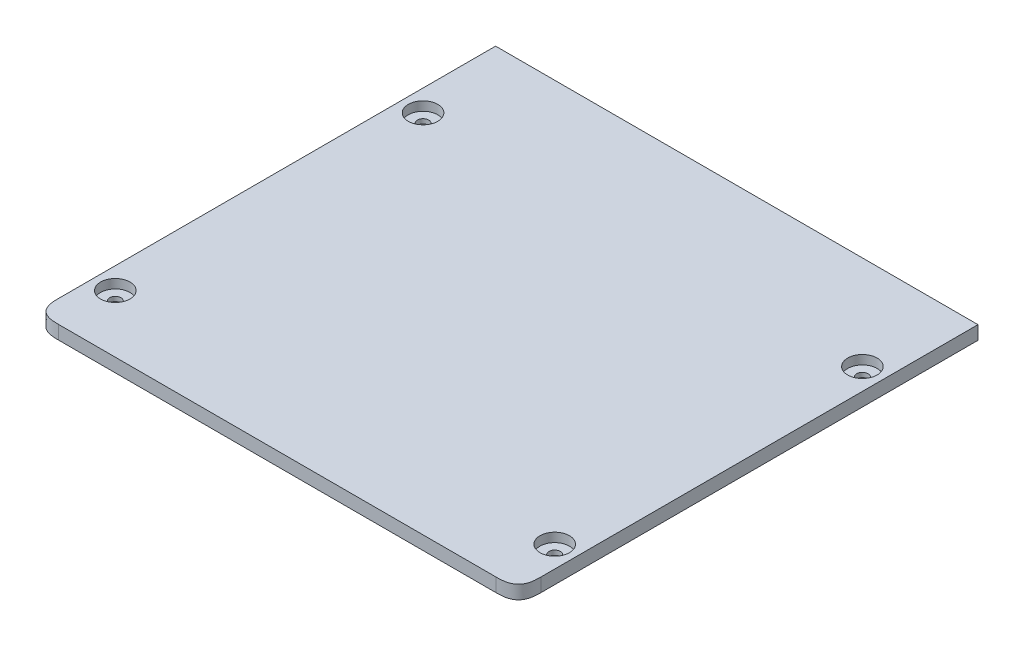
SolidWorks part; units mm, degrees
ref_plane "Front Plane" through (0, 0, 0) normal (0, 0, 1) x (1, 0, 0)
ref_plane "Top Plane" through (0, 0, 0) normal (0, 1, 0) x (1, 0, 0)
ref_plane "Right Plane" through (0, 0, 0) normal (1, 0, 0) x (0, 0, -1)
sketch "Sketch1" plane through (0, 0, 0) normal (0, 1, 0) x (1, 0, 0)
  line L1 (-53.25, -50.725) -> (53.25, -50.725)
  line L2 (-53.25, -50.725) -> (-53.25, 50.725)
  line L3 (-53.25, 50.725) -> (53.25, 50.725)
  line L4 (53.25, -50.725) -> (53.25, 50.725)
  line L5 (-53.25, -50.725) -> (53.25, 50.725) construction
  line L6 (-53.25, 50.725) -> (53.25, -50.725) construction
  point P0 (0, 0)
  dimension "D1" = 106.5
  dimension "D2" = 101.45
extrude "Boss-Extrude1" add sketch "Sketch1" along normal blind 3
sketch "Sketch2" plane through (0, 3, 0) normal (0, 1, 0) x (1, 0, 0)
  line L0 (-53.25, 50.725) -> (-53.25, -50.725) construction
  line L1 (53.25, 50.725) -> (-53.25, 50.725) construction
  line L2 (-53.25, -50.725) -> (53.25, -50.725) construction
  line L3 (0, -1.65) -> (0, 1.65) construction
  circle A1 centre (-48.5, -37.975) radius 1.25
  circle A2 centre (48.5, -37.975) radius 1.25
  circle A3 centre (-48.5, 29.965) radius 1.25
  circle A4 centre (48.5, 29.965) radius 1.25
  dimension "D1" = 2.5
  dimension "D4" = 2.5
  dimension "D2" = 20.76
  dimension "D5" = 4.75
  dimension "D6" = 12.75
extrude "Cut-Extrude1" cut sketch "Sketch2" against normal up to surface (3 mm away) up to face at (0, 0, 0)
sketch "Sketch3" plane through (0, 3, 0) normal (0, 1, 0) x (1, 0, 0)
  line L0 (0, -1.65) -> (0, 1.65) construction
  circle A1 centre (-48.5, -37.975) radius 3.25
  circle A2 centre (48.5, -37.975) radius 3.25
  circle A3 centre (-48.5, 29.965) radius 3.25
  circle A4 centre (48.5, 29.965) radius 3.25
  dimension "D1" = 6.5
  dimension "D2" = 6.5
extrude "Cut-Extrude2" cut sketch "Sketch3" against normal blind 2
fillet "Fillet1" radius 5 2 edges at (-53.25, 1.5, 50.725) (53.25, 1.5, 50.725) curvature continuous yes
sketch "Sketch4" plane through (0, 0, 0) normal (0, -1, 0) x (1, 0, 0)
  line L1 (-48.25, 50.725) -> (48.25, 50.725) construction
  line L2 (53.25, 45.725) -> (53.25, -50.725) construction
  circle A0 centre (16, 10.475) radius 27.25
  circle A1 centre (16, 10.475) radius 15
  dimension "D1" = 54.5
  dimension "D4" = 30
  dimension "D2" = 37.25
  dimension "D3" = 40.25
extrude "Boss-Extrude2" add sketch "Sketch4" along normal blind 10
sketch "Sketch5" plane through (0, 0, 0) normal (0, -1, 0) x (1, 0, 0)
  line L0 (16, 10.475) -> (16, -44.025) construction
  line L1 (16, -16.775) -> (16, -41.505)
  line L2 (16, -41.505) -> (-9, -41.505)
  line L3 (-9, -41.505) -> (-9, -38.38)
  line L4 (-9, -38.38) -> (-31.83, -38.38)
  line L5 (-31.83, -38.38) -> (-31.83, -43.755)
  line L6 (-31.83, -43.755) -> (-44.33, -43.755)
  line L7 (-44.33, -43.755) -> (-44.33, 37.4764)
  line L8 (-44.33, 37.4764) -> (-14.58, 37.4764)
  line L9 (-14.58, 37.4764) -> (-14.58, 39.4764)
  line L10 (-14.58, 39.4764) -> (11.92, 39.4764)
  line L11 (16, -16.775) -> (2, -11.2727)
  line L12 (2, -11.2727) -> (2, -20.2566)
  line L13 (2, -20.2566) -> (-9, -20.2566)
  line L14 (-9, -20.2566) -> (-9, -23.3965)
  line L15 (-9, -23.3965) -> (-31.83, -23.3965)
  line L16 (-31.83, -23.3965) -> (-31.83, 24.625)
  line L17 (-31.83, 24.625) -> (-12.58, 24.625)
  line L18 (-12.58, 24.625) -> (11.92, 39.4764)
  circle A1 centre (16, 10.475) radius 27.25 construction
  circle A2 centre (16, 10.475) radius 27.25 construction
  point P5 (16, -16.775)
  dimension "D1" = 24.73
  dimension "D2" = 25
  dimension "D3" = 3.125
  dimension "D4" = 22.83
  dimension "D5" = 5.375
  dimension "D6" = 12.5
  dimension "D7" = 81.2314
  dimension "D8" = 29.75
  dimension "D9" = 2
  dimension "D10" = 26.5
  dimension "D11" = 14
  dimension "D12" = 8.984
  dimension "D13" = 5.5023
  dimension "D14" = 11
  dimension "D15" = 3.1398
  dimension "D16" = 48.0215
  dimension "D17" = 19.25
extrude "Boss-Extrude3" add sketch "Sketch5" along normal blind 10
fillet "Fillet2" radius 8.5 7 edges at (2, -5, -12.9037) (-31.83, -5, -23.3965) (-31.83, -5, 24.625) (-44.33, -5, 37.4764) (16, -5, -41.505) (16, -5, -16.775) (-31.83, -5, -38.38)
